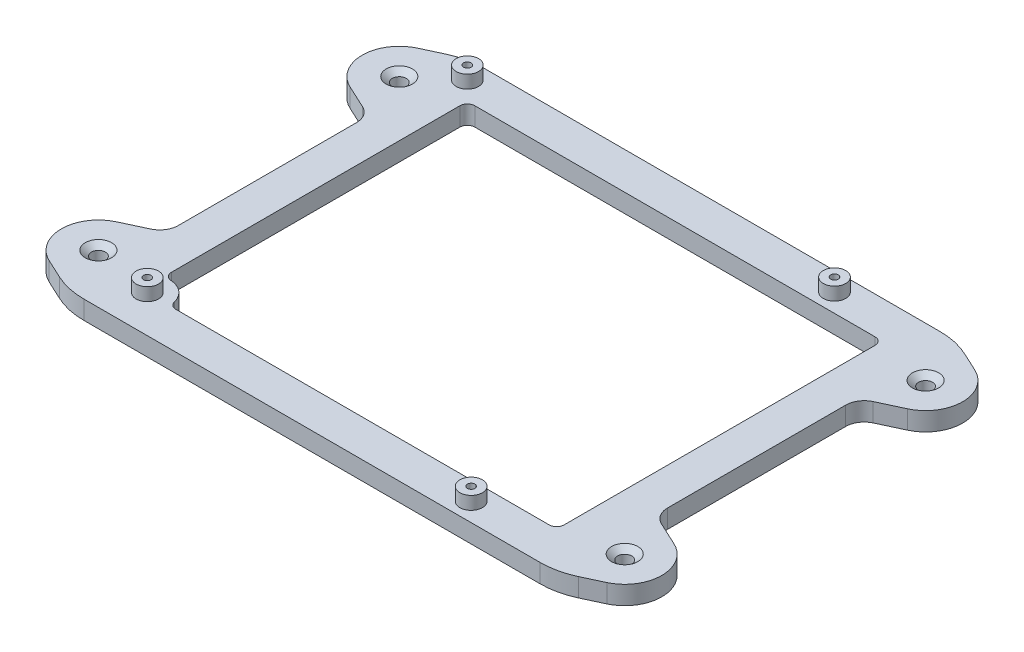
SolidWorks part; units mm, degrees
ref_plane "Front Plane" through (0, 0, 0) normal (0, 0, 1) x (1, 0, 0)
ref_plane "Top Plane" through (0, 0, 0) normal (0, 1, 0) x (1, 0, 0)
ref_plane "Right Plane" through (0, 0, 0) normal (1, 0, 0) x (0, 0, -1)
sketch "Quarter Base Sketch" plane through (0, 0, 0) normal (0, 1, 0) x (1, 0, 0)
  line L0 (0, 0) -> (0, 89.76) construction
  line L1 (0, 0) -> (-118.272, 0) construction
  line L2 (0, 53.955) -> (-66, 53.955)
  line L3 (-66, 53.955) -> (-75.2262, 49.6528)
  line L4 (-75.2262, 31.5266) -> (-66, 27.2244)
  line L5 (-66, 27.2244) -> (-66, 0)
  line L6 (-71, 40.5897) -> (-28.7156, 40.5897) construction
  line L7 (-66, 0) -> (-56, 0)
  line L8 (0, 43.955) -> (0, 53.955)
  line L9 (0, 43.955) -> (-56, 43.955)
  line L10 (-56, 43.955) -> (-56, 0)
  arc A0 (-75.2262, 49.6528) -> (-75.2262, 31.5266) centre (-71, 40.5897) ccw
  dimension "D2" = 10
  dimension "D1" = 132
  dimension "D3" = 25
  dimension "D4" = 5
  dimension "D5" = 107.91
  dimension "D6" = 10
  dimension "D7" = 10
extrude "Quarter Base" add sketch "Quarter Base Sketch" along normal blind 5
mirror "Base Mirror 1" about plane through (-66, 5, 0) normal (0, 0, -1) of bodies 101
mirror "Base Mirror 2" about plane through (0, 5, -43.955) normal (-1, 0, 0) of bodies 102
sketch "Corner Screw Expansion Sketch" plane through (0, 5, 0) normal (0, 1, 0) x (1, 0, 0)
  line L0 (66, -53.955) -> (-66, -53.955) construction
  circle A0 centre (-54.523, -43.876) radius 6.025
  point P2 (-63.667, -52.745)
  point P3 (38.06, 48.955)
  point P8 (-61, 48.955)
  point P9 (37.933, -48.955)
  dimension "D1" = 12.05
  dimension "D2" = 10.079
  dimension "D3" = 54.523
  dimension "D4" = 9.144
  dimension "D5" = 8.869
  dimension "D6" = 2.667
  dimension "D7" = 101.7
  dimension "D8" = 3.79
  dimension "D9" = 101.6
  dimension "D10" = 101.727
extrude "Corner Screw Expansion" add sketch "Corner Screw Expansion Sketch" against normal up to surface (5 mm away) up to face at (0, 0, 0)
sketch "Standoffs Extrusion Sketch" plane through (0, 5, 0) normal (0, 1, 0) x (1, 0, 0)
  circle A0 centre (-61, 48.955) radius 3.025
  circle A1 centre (-54.523, -43.876) radius 3.025
  circle A2 centre (37.933, -48.955) radius 3.025
  circle A3 centre (38.06, 48.955) radius 3.025
  point P12 (0, 0)
  dimension "D1" = 6.05
extrude "Standoffs Extrusion" add sketch "Standoffs Extrusion Sketch" along normal blind 3.5
sketch "Smoothieboard Screw Holes Sketch" plane through (0, 8.5, 0) normal (0, 1, 0) x (1, 0, 0)
  circle A0 centre (-54.523, -43.876) radius 1.025
  circle A1 centre (37.933, -48.955) radius 1.025
  circle A2 centre (38.06, 48.955) radius 1.025
  circle A3 centre (-61, 48.955) radius 1.025
  dimension "D1" = 2.05
extrude "Smoothieboard Screw Holes" cut sketch "Smoothieboard Screw Holes Sketch" against normal through all
hole_wizard "No. 6 Mounting Screws" positions "No. 6 Mounting Screws Position Sketch" profile "No. 6 Mounting Screws Profile Sketch" countersink size "#6" standard "ANSI Inch" end condition up to next
sketch3d "No. 6 Mounting Screws Position Sketch"
  arc A0 (75.2262, 5, -49.6528) -> (75.2262, 5, -31.5266) centre (71, 5, -40.5897) ccw construction
  arc A1 (75.2262, 5, 49.6528) -> (75.2262, 5, 31.5266) centre (71, 5, 40.5897) ccw construction
  arc A2 (-75.2262, 5, 49.6528) -> (-75.2262, 5, 31.5266) centre (-71, 5, 40.5897) ccw construction
  arc A3 (-75.2262, 5, -49.6528) -> (-75.2262, 5, -31.5266) centre (-71, 5, -40.5897) ccw construction
  point P0 (-71, 5, -40.5897)
  point P2 (-71, 5, 40.5897)
  point P4 (71, 5, 40.5897)
  point P6 (71, 5, -40.5897)
  point P11 (71, -5, -40.5897)
  point P15 (71, 15, 40.5897)
  point P19 (-71, -5, 40.5897)
  point P23 (-71, 15, -40.5897)
  point P24 (0, 0, 0)
sketch "No. 6 Mounting Screws Profile Sketch" plane through (-71, 5, -40.5897) normal (1, 0, 0) x (0, 0, 1)
  line L0 (0, 0) -> (0, 5)
  line L1 (0, 5) -> (1.8986, 5)
  line L2 (1.8986, 5) -> (1.8986, 1.38)
  line L3 (1.8986, 1.38) -> (3.5433, 0)
  line L5 (3.5433, 0) -> (0, 0)
  line L6 (-1.8986, 1.38) -> (-3.5433, 0) construction
  line L11 (0, -6.35) -> (0, 107.95) construction
  dimension "Thru Hole Dia." = 3.7973
  dimension "Thru Hole Depth" = 5
  dimension "Near C'Sink Dia." = 7.0866
  dimension "Near C'Sink Angle" = 100
fillet "Inside Corner Fillets" radius 2 5 edges at (-56, 2.5, 38.0348) (-48.4985, 2.5, 43.955) (56, 2.5, 43.955) (56, 2.5, -43.955) (-56, 2.5, -43.955)
fillet "Outside Corner Fillets 1" radius 5 4 edges at (-66, 2.5, 27.2244) (-66, 2.5, -27.2244) (66, 2.5, -27.2244) (66, 2.5, 27.2244)
fillet "Outside Corner Fillets 2" radius 20 4 edges at (66, 2.5, -53.955) (66, 2.5, 53.955) (-66, 2.5, 53.955) (-66, 2.5, -53.955)
